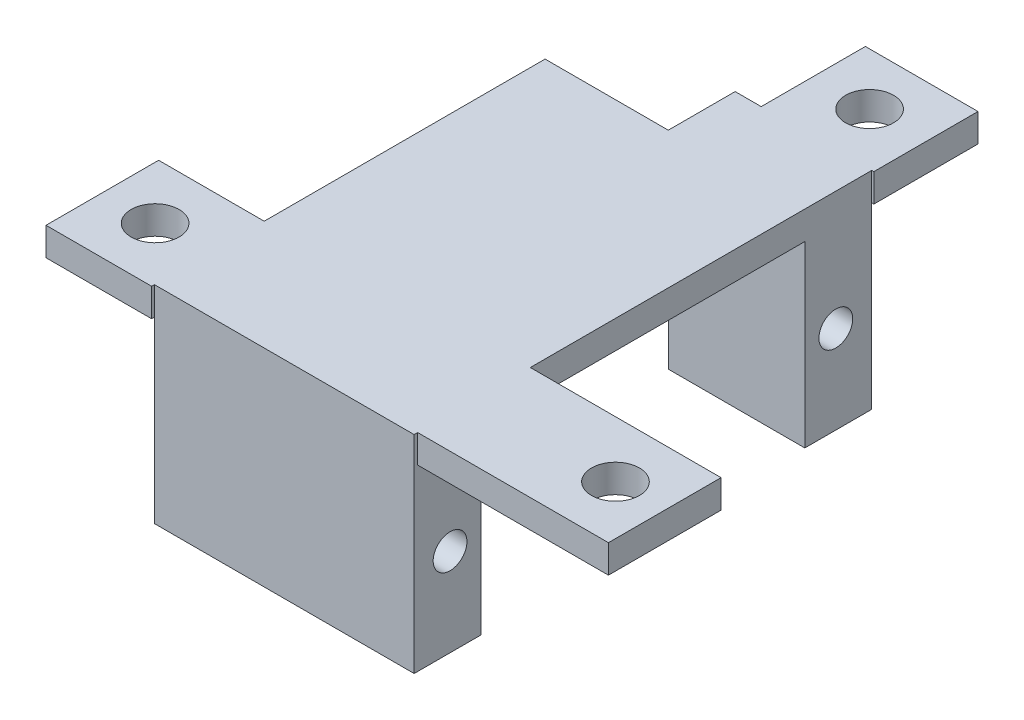
SolidWorks part; units mm, degrees
ref_plane "Front Plane" through (0, 0, 0) normal (0, 0, 1) x (1, 0, 0)
ref_plane "Top Plane" through (0, 0, 0) normal (0, 1, 0) x (1, 0, 0)
ref_plane "Right Plane" through (0, 0, 0) normal (1, 0, 0) x (0, 0, -1)
sketch "Sketch1" plane through (0, 0, 0) normal (0, 1, 0) x (1, 0, 0)
  line L0 (0.95, 16.25) -> (0.95, 11.5)
  line L1 (-17.5, -16.25) -> (17.5, -16.25)
  line L2 (-17.5, -16.25) -> (-17.5, 16.25)
  line L3 (-17.5, 16.25) -> (17.5, 16.25)
  line L4 (17.5, -16.25) -> (17.5, 16.25)
  line L5 (-17.5, -16.25) -> (17.5, 16.25) construction
  line L6 (-17.5, 16.25) -> (17.5, -16.25) construction
  line L7 (0.95, 11.5) -> (-17.5, 11.5)
  line L8 (0.95, -16.25) -> (0.95, -11.5)
  line L9 (0.95, -11.5) -> (-17.5, -11.5)
  line L10 (0.95, 11.5) -> (0.95, -11.5)
  line L11 (-8.75, 16.25) -> (-8.75, 11.5)
  line L12 (0.95, -8) -> (14.5, -8)
  line L13 (14.5, -8) -> (14.5, -16)
  line L14 (14.5, -16) -> (0.95, -16)
  line L15 (-6.9, 16.25) -> (-6.9, 23.65)
  line L16 (-6.9, 23.65) -> (1.1, 23.65)
  line L17 (1.1, 23.65) -> (1.1, 16.25)
  line L18 (-17.5, -16.45) -> (-25, -16.45)
  line L19 (-25, -16.45) -> (-25, -8.45)
  line L20 (-25, -8.45) -> (-17.5, -8.45)
  line L21 (-17.5, -16.45) -> (-17.5, -8.45)
  circle A0 centre (11, -12) radius 1.7
  circle A1 centre (-2.9, 19.95) radius 1.7
  circle A2 centre (-21.25, -12.45) radius 1.7
  point P0 (0, 0)
  point P11 (0.95, 0)
  point P36 (14.5, -12)
  point P38 (-21.25, -8.45)
  point P39 (-25, -12.45)
  point P41 (1.1, 19.95)
  point P42 (-2.9, 23.65)
  dimension "D6" = 3.4
  dimension "D7" = 3.4
  dimension "D8" = 3.4
  dimension "D1" = 32.5
  dimension "D2" = 23
  dimension "D3" = 8.75
  dimension "D4" = 18.45
  dimension "D5" = 16.55
  dimension "D9" = 11
  dimension "D10" = 12
  dimension "D11" = 8
  dimension "D12" = 12.45
  dimension "D13" = 8
  dimension "D14" = 21.25
  dimension "D15" = 8
  dimension "D16" = 2.9
  dimension "D17" = 19.95
  dimension "D18" = 14.5
extrude "Boss-Extrude1" add sketch "Sketch1" along normal blind 2 contours L18 L21 L2 L20 L19 A2 | A2 | L10 L7 L2 L9 | L8 L9 L2 L1 | L3 L11 L7 L0 | A1 | L17 L16 L15 L3 A1 | A0 | L14 L13 L12 L10 A0 region at (-3.9, 0, -13.875) region at (-2.975, 0, -16.359) region at (-8.275, 0, 0) region at (7.4256, 0, 12) region at (-8.275, 0, 13.875) region at (-17.6097, 0, 9.975) region at (11, 0, 12) region at (-2.9, 0, -19.95) region at (-21.25, 0, 12.45)
extrude "Boss-Extrude2" add sketch "Sketch1<5>" against normal blind 12.7 from surface contours L3 L11 L7 L0 | L8 L9 L2 L1 region at (-3.9, 0, -13.875) region at (-8.275, 0, 13.875) starting at face at (-6.4611, 0, -0.2778)
sketch "Sketch1<5>" plane through (0, 0, 0) normal (0, 1, 0) x (1, 0, 0) same geometry as "Sketch1"
extrude "Cut-Extrude1" cut sketch "Sketch1<6>" against normal through all both and the other way through all contours A1 | A0 | A2 region at (11, 0, 12) region at (-2.9, 0, -19.95) region at (-21.25, 0, 12.45)
sketch "Sketch1<6>" plane through (0, 0, 0) normal (0, 1, 0) x (1, 0, 0) same geometry as "Sketch1"
sketch "Sketch2" plane through (0, 0, 0) normal (1, 0, 0) x (0, 0, -1)
  line L0 (13.7, -6.45) -> (-13.7, -6.45) construction
  circle A0 centre (-13.7, -6.45) radius 1.2
  circle A1 centre (13.7, -6.45) radius 1.2
  point P4 (0, -6.45)
  dimension "D1" = 2.4
  dimension "D2" = 2.4
  dimension "D3" = 27.4
  dimension "D4" = 6.45
extrude "Cut-Extrude2" cut sketch "Sketch2" against normal blind 8 from surface starting at face at (0.95, -3.5667, 14.5833)
